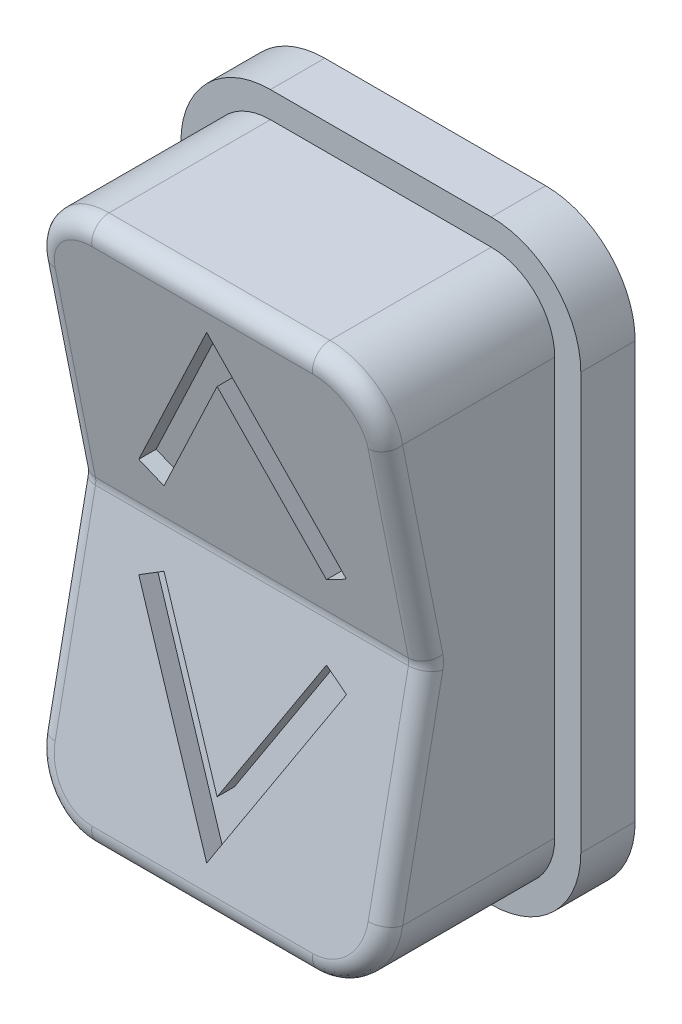
SolidWorks part; units mm, degrees
material "PET"
ref_plane "Front Plane" through (0, 0, 0) normal (0, 0, 1) x (1, 0, 0)
ref_plane "Top Plane" through (0, 0, 0) normal (0, 1, 0) x (1, 0, 0)
ref_plane "Right Plane" through (0, 0, 0) normal (1, 0, 0) x (0, 0, -1)
sketch "Sketch1" plane through (0, 0, 0) normal (0, 0, 1) x (1, 0, 0)
  line L0 (0, 0) -> (-5.08, 0) construction
  line L4 (0, 7.9375) -> (0, -7.9375) construction
  line L8 (3.2258, 7.9375) -> (-3.2258, 7.9375)
  line L9 (-5.08, 6.0833) -> (-5.08, -6.0833)
  line L10 (-3.2258, -7.9375) -> (3.2258, -7.9375)
  line L11 (5.08, -6.0833) -> (5.08, 6.0833)
  arc A8 (-3.2258, 7.9375) -> (-5.08, 6.0833) centre (-3.2258, 6.0833) ccw
  arc A9 (-5.08, -6.0833) -> (-3.2258, -7.9375) centre (-3.2258, -6.0833) ccw
  arc A10 (3.2258, -7.9375) -> (5.08, -6.0833) centre (3.2258, -6.0833) ccw
  arc A11 (5.08, 6.0833) -> (3.2258, 7.9375) centre (3.2258, 6.0833) ccw
  point P6 (0, 0)
  dimension "D3" = 1.8542
  dimension "D1" = 15.875
  dimension "D5" = 10.16
extrude "Boss-Extrude1" add sketch "Sketch1" against normal blind 5.334
sketch "Sketch11" plane through (0, 0, 0) normal (1, 0, 0) x (0, 0, -1)
  line L0 (0, -7.9375) -> (1.5875, 0)
  line L1 (1.5875, 0) -> (0, 0) construction
  line L2 (0, 7.9375) -> (0, -7.9375)
  line L3 (0, 7.9375) -> (1.5875, 0)
  dimension "D1" = 1.5875
extrude "Cut-Extrude4" cut sketch "Sketch11" against normal through all both and the other way through all
fillet "Fillet1" radius 0.508 11 edges at (0, -7.9375, 0) (-4.5369, -7.3944, -0.1086) (-5.08, -3.0417, -0.9792) (5.08, -3.0417, -0.9792) (4.5369, -7.3944, -0.1086) (5.08, 3.0417, -0.9792) (0, 0, -1.5875) (-5.08, 3.0416, -0.9792) (-4.5369, 7.3944, -0.1086) (0, 7.9375, 0) (4.5369, 7.3944, -0.1086)
sketch "Sketch4" plane through (0, 0, -5.334) normal (0, 0, -1) x (-1, 0, 0)
  line L8 (-5.842, 6.0833) -> (-5.842, -6.0833)
  line L9 (-3.2258, -8.6995) -> (3.2258, -8.6995)
  line L10 (5.842, -6.0833) -> (5.842, 6.0833)
  line L11 (3.2258, 8.6995) -> (-3.2258, 8.6995)
  line L12 (-5.842, 6.0833) -> (-5.842, -6.0833)
  line L13 (-3.2258, -8.6995) -> (3.2258, -8.6995)
  line L14 (5.842, -6.0833) -> (5.842, 6.0833)
  line L15 (3.2258, 8.6995) -> (-3.2258, 8.6995)
  arc A8 (-3.2258, 8.6995) -> (-5.842, 6.0833) centre (-3.2258, 6.0833) ccw
  arc A9 (-5.842, -6.0833) -> (-3.2258, -8.6995) centre (-3.2258, -6.0833) ccw
  arc A10 (3.2258, -8.6995) -> (5.842, -6.0833) centre (3.2258, -6.0833) ccw
  arc A11 (5.842, 6.0833) -> (3.2258, 8.6995) centre (3.2258, 6.0833) ccw
  arc A12 (-3.2258, 8.6995) -> (-5.842, 6.0833) centre (-3.2258, 6.0833) ccw
  arc A13 (-5.842, -6.0833) -> (-3.2258, -8.6995) centre (-3.2258, -6.0833) ccw
  arc A14 (3.2258, -8.6995) -> (5.842, -6.0833) centre (3.2258, -6.0833) ccw
  arc A15 (5.842, 6.0833) -> (3.2258, 8.6995) centre (3.2258, 6.0833) ccw
  dimension "D1" = 0.762
extrude "Boss-Extrude2" add sketch "Sketch4" along normal blind 1.5875
hole_wizard "#56 (0.0465) Diameter Hole1" positions "Sketch6" profile "Sketch7" hole size "#56" standard "ANSI Inch"
sketch "Sketch6" plane through (0, 0, -6.9215) normal (0, 0, -1) x (-1, 0, 0)
  line L1 (-3.2258, 7.9375) -> (3.2258, 7.9375) construction
  line L3 (3.2258, -7.9375) -> (-3.2258, -7.9375) construction
  line L4 (0, 7.9375) -> (0, 3.9688) construction
  line L5 (0, 3.9688) -> (0, 0) construction
  line L7 (0, 0) -> (0, -3.9688) construction
  line L8 (0, -3.9688) -> (0, -7.9375) construction
  point P33 (0, -5.9531)
  point P35 (0, 5.9531)
sketch "Sketch7" plane through (0, -5.9531, -6.9215) normal (1, 0, 0) x (0, 1, 0)
  line L0 (0, 0) -> (0, 5.08)
  line L1 (0, 5.08) -> (0.5905, 5.08)
  line L2 (0.5905, 5.08) -> (0.5905, 0)
  line L5 (0.5905, 0) -> (0, 0)
  line L10 (0, 5.08) -> (-0.5906, 5.08) construction
  line L11 (0, -6.35) -> (0, 107.95) construction
  dimension "Hole Dia." = 1.1811
  dimension "Hole Depth" = 5.08
  dimension "Drill Angle" = 180
sketch "Sketch12" plane through (0, 0, 0) normal (0, 0, 1) x (1, 0, 0)
  line L0 (0, 5.9531) -> (-2.7038, 1.27) construction
  line L1 (0, 7.3299) -> (0, 0) construction
  line L2 (3.2258, 7.3299) -> (-3.2258, 7.3299) construction
  line L3 (0, 5.9531) -> (2.7038, 1.27) construction
  line L4 (0, 0) -> (5.842, 0) construction
  line L5 (5.842, 6.0833) -> (5.842, -6.0833) construction
  line L8 (0, 6.7151) -> (3.0338, 1.4605)
  line L9 (0, 6.7151) -> (-3.0338, 1.4605)
  line L12 (0, 5.1911) -> (2.3738, 1.0795)
  line L13 (0, 5.1911) -> (-2.3738, 1.0795)
  line L16 (3.0338, 1.4605) -> (2.3738, 1.0795)
  line L17 (-3.0338, 1.4605) -> (-2.3738, 1.0795)
  dimension "D1" = 30
  dimension "D2" = 1.27
  dimension "D3" = 0.381
  dimension "D4" = 0.381
extrude "Cut-Extrude5" cut sketch "Sketch12" against normal blind 0.508 from surface starting at face at (0, 4.564, -0.6747)
sketch "Sketch13" plane through (0, 0, 0) normal (0, 0, 1) x (1, 0, 0)
  line L0 (0, 0) -> (5.842, 0) construction
  line L1 (2.3738, -1.0795) -> (3.0338, -1.4605)
  line L2 (0, -5.1911) -> (2.3738, -1.0795)
  line L3 (-2.3738, -1.0795) -> (0, -5.1911)
  line L4 (-3.0338, -1.4605) -> (-2.3738, -1.0795)
  line L5 (0, -6.7151) -> (-3.0338, -1.4605)
  line L6 (3.0338, 1.4605) -> (0, 6.7151)
  line L7 (0, 6.7151) -> (-3.0338, 1.4605)
  line L8 (-3.0338, 1.4605) -> (-2.3738, 1.0795)
  line L9 (-2.3738, 1.0795) -> (0, 5.1911)
  line L10 (0, 5.1911) -> (2.3738, 1.0795)
  line L11 (2.3738, 1.0795) -> (3.0338, 1.4605)
  line L12 (3.0338, 1.4605) -> (0, 6.7151) construction
  line L13 (0, 6.7151) -> (-3.0338, 1.4605) construction
  line L14 (-3.0338, 1.4605) -> (-2.3738, 1.0795) construction
  line L15 (-2.3738, 1.0795) -> (0, 5.1911) construction
  line L16 (0, 5.1911) -> (2.3738, 1.0795) construction
  line L17 (2.3738, 1.0795) -> (3.0338, 1.4605) construction
  line L18 (3.0338, -1.4605) -> (0, -6.7151)
  dimension "D1" = 0
extrude "Cut-Extrude6" cut sketch "Sketch13" against normal blind 0.508 from surface starting at face at (0, -4.564, -0.6747)
